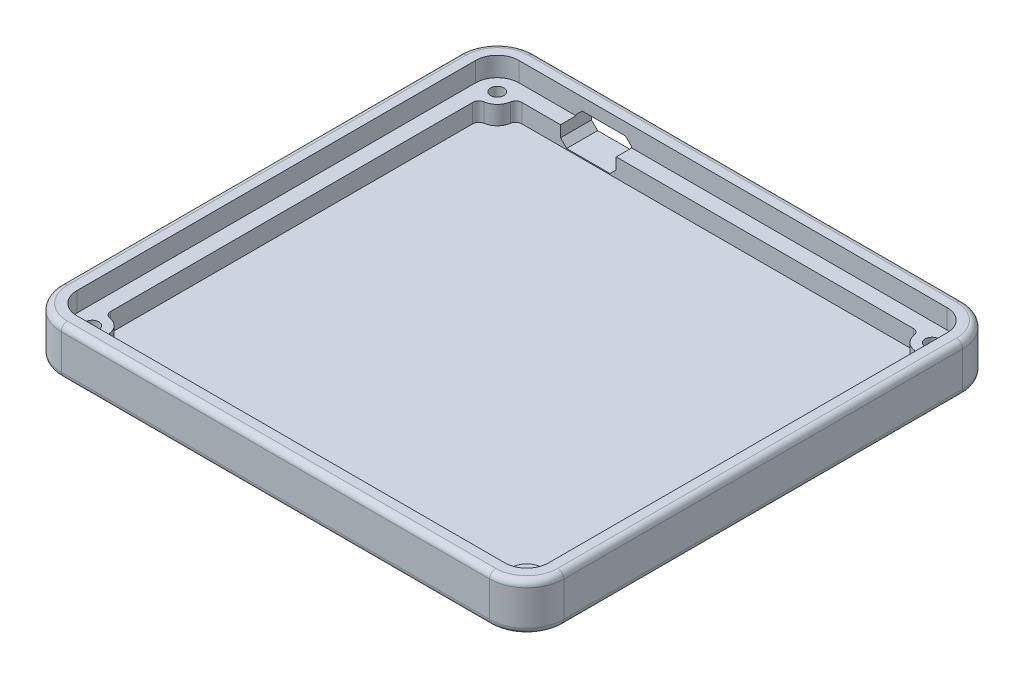
SolidWorks part; units mm, degrees
material "ABS"
ref_plane "Front Plane" through (0, 0, 0) normal (0, 0, 1) x (1, 0, 0)
ref_plane "Top Plane" through (0, 0, 0) normal (0, 1, 0) x (1, 0, 0)
ref_plane "Right Plane" through (0, 0, 0) normal (1, 0, 0) x (0, 0, -1)
sketch "Sketch2" plane through (0, 0, 0) normal (0, 1, 0) x (1, 0, 0)
  line L1 (-69.195, 71.435) -> (69.195, 71.435)
  line L2 (-76.195, 64.435) -> (-76.195, -64.435)
  line L3 (-69.195, -71.435) -> (69.195, -71.435)
  line L4 (76.195, 64.435) -> (76.195, -64.435)
  line L5 (-76.195, 71.435) -> (76.195, -71.435) construction
  line L6 (-76.195, -71.435) -> (76.195, 71.435) construction
  arc A0 (-76.195, -64.435) -> (-69.195, -71.435) centre (-69.195, -64.435) ccw
  arc A1 (-69.195, 71.435) -> (-76.195, 64.435) centre (-69.195, 64.435) ccw
  arc A2 (69.195, 71.435) -> (76.195, 64.435) centre (69.195, 64.435) cw
  arc A3 (69.195, -71.435) -> (76.195, -64.435) centre (69.195, -64.435) ccw
  point P0 (0, 0)
  dimension "D3" = 7
  dimension "D1" = 152.39
  dimension "D2" = 142.87
extrude "Boss-Extrude2" add sketch "Sketch2" along normal blind 3
sketch "Sketch3" plane through (0, 3, 0) normal (0, 1, 0) x (1, 0, 0)
  line L0 (-69.195, -71.435) -> (69.195, -71.435) construction
  line L1 (76.195, -64.435) -> (76.195, 64.435) construction
  line L2 (69.195, 71.435) -> (-69.195, 71.435) construction
  line L3 (-76.195, 64.435) -> (-76.195, -64.435) construction
  line L4 (-69.195, -71.435) -> (69.195, -71.435)
  line L5 (76.195, -64.435) -> (76.195, 64.435)
  line L6 (69.195, 71.435) -> (-69.195, 71.435)
  line L7 (-76.195, 64.435) -> (-76.195, -64.435)
  line L8 (0, -80.5945) -> (0, 82.9206) construction
  line L9 (9.041, 0) -> (-113.0904, 0) construction
  line L10 (-81.195, 64.435) -> (-81.195, -64.435)
  line L11 (-69.195, -76.435) -> (69.195, -76.435)
  line L12 (81.195, -64.435) -> (81.195, 64.435)
  line L13 (69.195, 76.435) -> (-69.195, 76.435)
  line L14 (-71.195, 60.44) -> (-71.195, -60.44)
  line L15 (-65.2, -66.435) -> (65.2, -66.435)
  line L16 (71.195, -60.44) -> (71.195, 60.44)
  line L17 (65.2, 66.435) -> (-65.2, 66.435)
  line L18 (-71.195, 60.44) -> (-70.195, 60.44)
  line L19 (-65.2, 66.435) -> (-65.2, 65.435)
  line L20 (-71.195, 64.435) -> (-71.195, -64.435) construction
  line L21 (69.195, 66.435) -> (-69.195, 66.435) construction
  line L22 (65.2, 66.435) -> (65.2, 65.435)
  line L23 (71.195, 60.44) -> (70.195, 60.44)
  line L24 (65.2, -66.435) -> (65.2, -65.435)
  line L25 (71.195, -60.44) -> (70.195, -60.44)
  line L26 (-65.2, -66.435) -> (-65.2, -65.435)
  line L27 (-71.195, -60.44) -> (-70.195, -60.44)
  line L28 (-69.195, -66.435) -> (69.195, -66.435) construction
  line L29 (71.195, -64.435) -> (71.195, 64.435) construction
  arc A0 (-76.195, -64.435) -> (-69.195, -71.435) centre (-69.195, -64.435) ccw construction
  arc A1 (69.195, -71.435) -> (76.195, -64.435) centre (69.195, -64.435) ccw construction
  arc A2 (76.195, 64.435) -> (69.195, 71.435) centre (69.195, 64.435) ccw construction
  arc A3 (-69.195, 71.435) -> (-76.195, 64.435) centre (-69.195, 64.435) ccw construction
  arc A4 (-76.195, -64.435) -> (-69.195, -71.435) centre (-69.195, -64.435) ccw
  arc A5 (69.195, -71.435) -> (76.195, -64.435) centre (69.195, -64.435) ccw
  arc A6 (76.195, 64.435) -> (69.195, 71.435) centre (69.195, 64.435) ccw
  arc A7 (-69.195, 71.435) -> (-76.195, 64.435) centre (-69.195, 64.435) ccw
  circle A9 centre (-70.2, -65.44) radius 2.15
  circle A10 centre (70.2, -65.44) radius 2.15
  circle A11 centre (70.2, 65.44) radius 2.15
  circle A12 centre (-70.2, 65.44) radius 2.15
  arc A13 (-81.195, -64.435) -> (-69.195, -76.435) centre (-69.195, -64.435) ccw
  arc A14 (69.195, -76.435) -> (81.195, -64.435) centre (69.195, -64.435) ccw
  arc A15 (81.195, 64.435) -> (69.195, 76.435) centre (69.195, 64.435) ccw
  arc A16 (-69.195, 76.435) -> (-81.195, 64.435) centre (-69.195, 64.435) ccw
  arc A21 (-70.195, 60.44) -> (-65.2, 65.435) centre (-70.195, 65.435) ccw
  arc A22 (70.195, 60.44) -> (65.2, 65.435) centre (70.195, 65.435) cw
  arc A23 (-69.195, 66.435) -> (-71.195, 64.435) centre (-69.195, 64.435) ccw construction
  arc A24 (70.195, -60.44) -> (65.2, -65.435) centre (70.195, -65.435) ccw
  arc A25 (-70.195, -60.44) -> (-65.2, -65.435) centre (-70.195, -65.435) cw
  arc A26 (-71.195, -64.435) -> (-69.195, -66.435) centre (-69.195, -64.435) ccw construction
  arc A27 (69.195, -66.435) -> (71.195, -64.435) centre (69.195, -64.435) ccw construction
  arc A28 (71.195, 64.435) -> (69.195, 66.435) centre (69.195, 64.435) ccw construction
  arc M10 (-76.195, -64.435) -> (-69.195, -71.435) centre (-69.195, -64.435) ccw
  line M11 (-69.195, -71.435) -> (69.195, -71.435)
  arc M12 (69.195, -71.435) -> (76.195, -64.435) centre (69.195, -64.435) ccw
  line M13 (76.195, -64.435) -> (76.195, 64.435)
  arc M14 (76.195, 64.435) -> (69.195, 71.435) centre (69.195, 64.435) ccw
  line M15 (69.195, 71.435) -> (-69.195, 71.435)
  arc M16 (-69.195, 71.435) -> (-76.195, 64.435) centre (-69.195, 64.435) ccw
  line M17 (-76.195, 64.435) -> (-76.195, -64.435)
  dimension "D1" = 65.44
  dimension "D2" = 4.3
  dimension "D3" = 70.2
  dimension "D4" = 5
  dimension "D6" = 1
  dimension "D7" = 5
  dimension "D8" = 1
  dimension "D9" = 5
  dimension "D5" = 5
extrude "Boss-Extrude3" add sketch "Sketch3" along normal blind 6 and the other way blind 3 contours L13 A16 L10 A13 L11 A14 L12 A15 M10 M17 M16 M15 M14 M13 M12 M11 | L17 L16 L15 L14 M17 M10 M11 M12 M13 M14 M15 M16 region at (-72.6677, 3, 67.9077) region at (-76.1033, 3, -71.3433)
sketch "Sketch8" plane through (0, 9, 0) normal (0, 1, 0) x (1, 0, 0)
  line L0 (-69.195, -76.435) -> (69.195, -76.435) construction
  line L1 (81.195, -64.435) -> (81.195, 64.435) construction
  line L2 (69.195, 76.435) -> (-69.195, 76.435) construction
  line L3 (-81.195, 64.435) -> (-81.195, -64.435) construction
  line L4 (76.195, -64.435) -> (76.195, 64.435)
  line L5 (69.195, 71.435) -> (-69.195, 71.435)
  line L6 (-76.195, 64.435) -> (-76.195, -64.435)
  line L7 (-69.195, -71.435) -> (69.195, -71.435)
  line L8 (76.195, -64.435) -> (76.195, 64.435)
  line L9 (69.195, 71.435) -> (-69.195, 71.435)
  line L10 (-76.195, 64.435) -> (-76.195, -64.435)
  line L11 (-69.195, -71.435) -> (69.195, -71.435)
  line L12 (-69.195, -76.435) -> (69.195, -76.435)
  line L13 (81.195, -64.435) -> (81.195, 64.435)
  line L14 (69.195, 76.435) -> (-69.195, 76.435)
  line L15 (-81.195, 64.435) -> (-81.195, -64.435)
  line L16 (-76.195, 64.435) -> (-76.195, -64.435)
  line L17 (-69.195, -71.435) -> (69.195, -71.435)
  line L18 (76.195, -64.435) -> (76.195, 64.435)
  line L19 (69.195, 71.435) -> (-69.195, 71.435)
  arc A0 (-81.195, -64.435) -> (-69.195, -76.435) centre (-69.195, -64.435) ccw construction
  arc A1 (69.195, -76.435) -> (81.195, -64.435) centre (69.195, -64.435) ccw construction
  arc A2 (81.195, 64.435) -> (69.195, 76.435) centre (69.195, 64.435) ccw construction
  arc A3 (-69.195, 76.435) -> (-81.195, 64.435) centre (-69.195, 64.435) ccw construction
  arc A4 (76.195, 64.435) -> (69.195, 71.435) centre (69.195, 64.435) ccw
  arc A5 (-69.195, 71.435) -> (-76.195, 64.435) centre (-69.195, 64.435) ccw
  arc A6 (-76.195, -64.435) -> (-69.195, -71.435) centre (-69.195, -64.435) ccw
  arc A7 (69.195, -71.435) -> (76.195, -64.435) centre (69.195, -64.435) ccw
  arc A8 (76.195, 64.435) -> (69.195, 71.435) centre (69.195, 64.435) ccw
  arc A9 (-69.195, 71.435) -> (-76.195, 64.435) centre (-69.195, 64.435) ccw
  arc A10 (-76.195, -64.435) -> (-69.195, -71.435) centre (-69.195, -64.435) ccw
  arc A11 (69.195, -71.435) -> (76.195, -64.435) centre (69.195, -64.435) ccw
  arc A12 (-81.195, -64.435) -> (-69.195, -76.435) centre (-69.195, -64.435) ccw
  arc A13 (69.195, -76.435) -> (81.195, -64.435) centre (69.195, -64.435) ccw
  arc A14 (81.195, 64.435) -> (69.195, 76.435) centre (69.195, 64.435) ccw
  arc A15 (-69.195, 76.435) -> (-81.195, 64.435) centre (-69.195, 64.435) ccw
  arc A16 (-76.195, -64.435) -> (-69.195, -71.435) centre (-69.195, -64.435) ccw
  arc A17 (69.195, -71.435) -> (76.195, -64.435) centre (69.195, -64.435) ccw
  arc A18 (76.195, 64.435) -> (69.195, 71.435) centre (69.195, 64.435) ccw
  arc A19 (-69.195, 71.435) -> (-76.195, 64.435) centre (-69.195, 64.435) ccw
  line M17 (69.195, 76.435) -> (-69.195, 76.435)
  arc M18 (-69.195, 76.435) -> (-81.195, 64.435) centre (-69.195, 64.435) ccw
  line M19 (-81.195, 64.435) -> (-81.195, -64.435)
  arc M20 (-81.195, -64.435) -> (-69.195, -76.435) centre (-69.195, -64.435) ccw
  line M21 (-69.195, -76.435) -> (69.195, -76.435)
  arc M22 (69.195, -76.435) -> (81.195, -64.435) centre (69.195, -64.435) ccw
  line M23 (81.195, -64.435) -> (81.195, 64.435)
  arc M24 (81.195, 64.435) -> (69.195, 76.435) centre (69.195, 64.435) ccw
  dimension "D1" = 0
  dimension "D2" = 5
extrude "Boss-Extrude4" add sketch "Sketch8" along normal blind 6.28 contours A11 L11 A10 L10 A9 L9 A8 L8 M24 M17 M18 M19 M20 M21 M22 M23 region at (-76.1033, 9, 71.3433)
sketch "Sketch9" plane through (0, 0, -76.435) normal (0, 0, -1) x (-1, 0, 0)
  line L0 (81.195, 0) -> (81.195, 15.28) construction
  line L7 (48.765, 11.345) -> (34.765, 11.345)
  line L8 (34.765, 11.345) -> (32.765, 9.345)
  line L14 (50.765, 9.345) -> (48.765, 11.345)
  line L15 (54.9775, 7.345) -> (29.0731, 7.345) construction
  line L16 (32.765, 9.345) -> (32.765, 5.345)
  line L17 (50.765, 9.345) -> (50.765, 5.345)
  line L18 (41.765, 11.345) -> (41.765, 5.8424) construction
  line L19 (-69.195, 0) -> (69.195, 0) construction
  line L20 (50.765, 5.345) -> (48.765, 3.345)
  line L21 (48.765, 3.345) -> (34.765, 3.345)
  line L22 (34.765, 3.345) -> (32.765, 5.345)
  point P7 (50.765, 7.345)
  point P20 (32.765, 7.345)
  dimension "D2" = 7.345
  dimension "D1" = 39.43
  dimension "D5" = 4
  dimension "D6" = 2
  dimension "D7" = 18
  dimension "D8" = 14
extrude "Cut-Extrude1" cut sketch "Sketch9" against normal blind 10
fillet "Fillet1" radius 2 8 edges at (-65.2, 6, -66.435) (-71.195, 6, -60.44) (-71.195, 6, 60.44) (-65.2, 6, 66.435) (71.195, 6, 60.44) (65.2, 6, 66.435) (65.2, 6, -66.435) (71.195, 6, -60.44)
sketch "Sketch11" plane through (0, 3, 0) normal (0, 1, 0) x (1, 0, 0)
  circle A0 centre (-70.2, 65.44) radius 2.15
  circle A1 centre (70.2, 65.44) radius 2.15
  circle A2 centre (70.2, -65.4964) radius 2.15
  circle A3 centre (-70.2, -65.44) radius 2.15
  dimension "D1" = 4.3
  dimension "D2" = 4.3
  dimension "D3" = 4.3
  dimension "D4" = 4.3
extrude "Cut-Extrude3" cut sketch "Sketch11" against normal through all both and the other way through all contours A3 | A2 | A1 | A0 region at (-70.2, 3, -65.44) region at (70.2, 3, -65.44) region at (70.2, 3, 65.4964) region at (-70.2, 3, 65.44)
sketch "Sketch10" plane through (0, 0, 0) normal (0, -1, 0) x (1, 0, 0)
  line L0 (0, -76.435) -> (0, 105.632) construction
  line L1 (69.195, -76.435) -> (-69.195, -76.435) construction
  line L2 (-81.195, 0) -> (91.4068, 0) construction
  line L3 (-81.195, -64.435) -> (-81.195, 64.435) construction
  line L4 (68.1793, 61.94) -> (66.1585, 65.44)
  line L5 (-66.1585, 65.44) -> (-68.1793, 68.94)
  line L6 (-68.1793, 68.94) -> (-72.2207, 68.94)
  line L7 (-72.2207, 68.94) -> (-74.2415, 65.44)
  line L8 (-74.2415, 65.44) -> (-72.2207, 61.94)
  line L9 (-72.2207, 61.94) -> (-68.1793, 61.94)
  line L10 (-68.1793, 61.94) -> (-66.1585, 65.44)
  line L11 (72.2207, 61.94) -> (68.1793, 61.94)
  line L12 (74.2415, 65.44) -> (72.2207, 61.94)
  line L13 (72.2207, 68.94) -> (74.2415, 65.44)
  line L14 (68.1793, 68.94) -> (72.2207, 68.94)
  line L15 (66.1585, 65.44) -> (68.1793, 68.94)
  line L16 (72.2207, -61.94) -> (68.1793, -61.94)
  line L17 (74.2415, -65.44) -> (72.2207, -61.94)
  line L18 (72.2207, -68.94) -> (74.2415, -65.44)
  line L19 (68.1793, -68.94) -> (72.2207, -68.94)
  line L20 (66.1585, -65.44) -> (68.1793, -68.94)
  line L21 (68.1793, -61.94) -> (66.1585, -65.44)
  line L22 (-68.1793, -61.94) -> (-66.1585, -65.44)
  line L23 (-72.2207, -61.94) -> (-68.1793, -61.94)
  line L24 (-74.2415, -65.44) -> (-72.2207, -61.94)
  line L25 (-72.2207, -68.94) -> (-74.2415, -65.44)
  line L26 (-68.1793, -68.94) -> (-72.2207, -68.94)
  line L27 (-66.1585, -65.44) -> (-68.1793, -68.94)
  line L28 (-70.2, 65.44) -> (-62.8389, 65.44)
  circle A0 centre (-70.2, 65.44) radius 3.5 construction
  circle A1 centre (-70.2, 65.44) radius 2.15 construction
  dimension "D3" = 7
extrude "Cut-Extrude2" cut sketch "Sketch10" against normal blind 4 contours L9 L10 L5 L6 L7 L8 | L12 L11 L4 L15 L14 L13 | L22 L27 L26 L25 L24 L23 | L17 L16 L21 L20 L19 L18 region at (-67.2615, 0, 63.7435)
fillet "Fillet4" radius 2 16 edges at (-77.6803, 0, -72.9203) (0, 0, -76.435) (77.6803, 0, -72.9203) (81.195, 0, 0) (77.6803, 0, 72.9203) (0, 0, 76.435) (-77.6803, 0, 72.9203) (-77.6803, 15.28, -72.9203) (0, 15.28, -76.435) (77.6803, 15.28, -72.9203) (81.195, 15.28, 0) (77.6803, 15.28, 72.9203) (0, 15.28, 76.435) (-77.6803, 15.28, 72.9203) (-81.195, 0, 0) (-81.195, 15.28, 0)
sketch "Sketch13" plane through (0, 0, 0) normal (0, -1, 0) x (1, 0, 0)
  line L0 (0, 15.661) -> (0, -101.1595) construction
  line L1 (-15, -31.435) -> (15, -31.435) construction
  line L2 (-15, -25.435) -> (15, -25.435)
  line L3 (-15, -37.435) -> (15, -37.435)
  line L4 (69.195, -76.435) -> (-69.195, -76.435) construction
  arc A0 (-15, -25.435) -> (-15, -37.435) centre (-15, -31.435) ccw
  arc A1 (15, -37.435) -> (15, -25.435) centre (15, -31.435) ccw
  point P5 (0, -31.435)
  dimension "D1" = 30
  dimension "D2" = 45
  dimension "D3" = 12
extrude "Cut-Extrude5" cut sketch "Sketch13" against normal blind 2
sketch "Sketch14" plane through (0, 0, 0) normal (0, -1, 0) x (1, 0, 0)
  line L0 (0, 20.3696) -> (0, -82.809) construction
  line L1 (69.195, -76.435) -> (-69.195, -76.435) construction
  circle A0 centre (-55, -56.435) radius 10
  circle A1 centre (55, -56.435) radius 10
  dimension "D3" = 20
  dimension "D1" = 55
  dimension "D2" = 20
extrude "Cut-Extrude6" cut sketch "Sketch14" against normal blind 2
